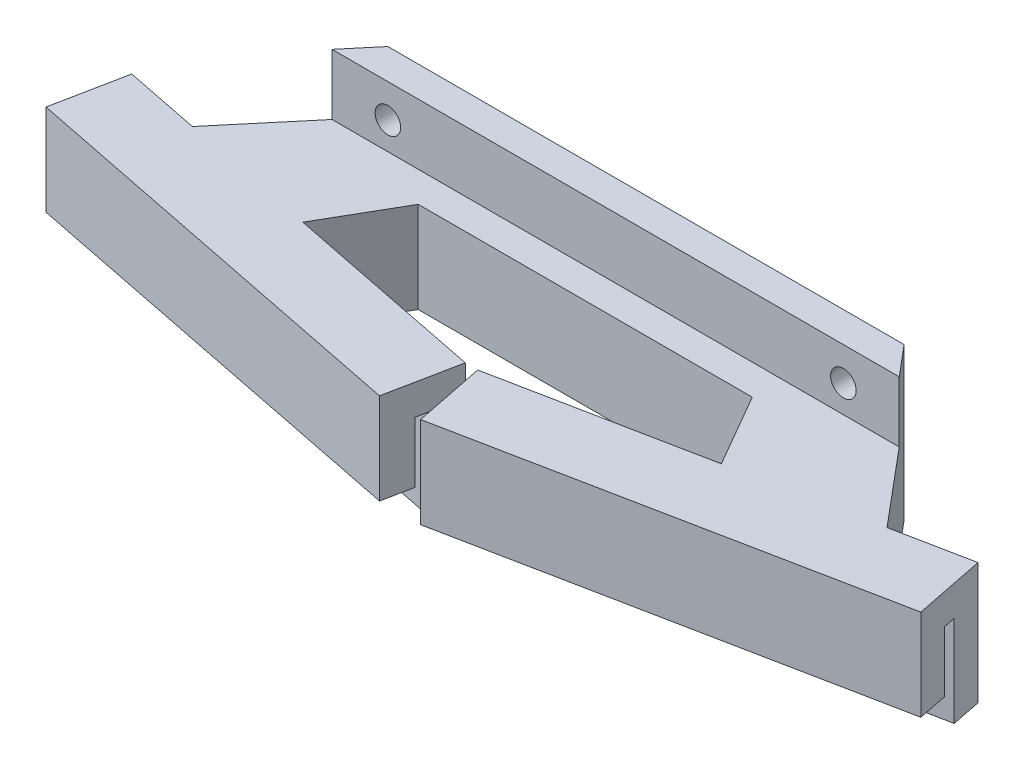
SolidWorks part; units mm, degrees
material "ABS"
ref_plane "Front Plane" through (0, 0, 0) normal (0, 0, 1) x (1, 0, 0)
ref_plane "Top Plane" through (0, 0, 0) normal (0, 1, 0) x (1, 0, 0)
ref_plane "Right Plane" through (0, 0, 0) normal (1, 0, 0) x (0, 0, -1)
ref_axis "X" through (-88.99, 0, 0) along (1, 0, 0)
ref_axis "Y" through (0, 55, 0) along (0, -1, 0)
ref_axis "Z" through (0, 0, -88.99) along (0, 0, 1)
sketch "Sketch1" plane through (0, 0, 0) normal (0, 1, 0) x (1, 0, 0)
  line L0 (27.1702, -94.8196) -> (27.5625, -96.7807) construction
  line L1 (27.1702, -94.8196) -> (27.5625, -96.7807)
  line L2 (22.7661, -96.7807) -> (23.1583, -94.8196) construction
  line L3 (-45.8746, -83.0526) -> (22.7661, -96.7807) construction
  line L4 (22.7661, -96.7807) -> (23.1583, -94.8196)
  line L5 (27.5625, -96.7807) -> (96.2031, -83.0526) construction
  line L6 (23.1583, -94.8196) -> (-45.4823, -81.0914)
  line L7 (-45.4823, -81.0914) -> (-45.8746, -83.0526)
  line L8 (-45.8746, -83.0526) -> (22.7661, -96.7807)
  line L9 (27.1702, -94.8196) -> (95.8109, -81.0914)
  line L10 (95.8109, -81.0914) -> (96.2031, -83.0526)
  line L11 (96.2031, -83.0526) -> (27.5625, -96.7807)
  dimension "D3" = 2
  dimension "D4" = 2
  dimension "D7" = 70
  dimension "D8" = 70
extrude "Boss-Extrude1" add sketch "Sketch1" along normal blind 5
sketch "Sketch2" plane through (0, 5, 0) normal (0, 1, 0) x (1, 0, 0)
  line L0 (0, 0) -> (0, 33.2136) construction
  line L1 (22.9622, -95.8001) -> (-45.6785, -82.072) construction
  line L2 (22.7661, -96.7807) -> (23.1583, -94.8196) construction
  line L3 (-45.4823, -81.0914) -> (-45.8746, -83.0526) construction
  line L4 (-45.4823, -81.0914) -> (-44.5018, -76.1885)
  line L5 (-44.5018, -76.1885) -> (24.1389, -89.9167)
  line L6 (24.1389, -89.9167) -> (23.1583, -94.8196)
  line L7 (23.1583, -94.8196) -> (-45.4823, -81.0914) construction
  line L8 (23.1583, -94.8196) -> (-45.4823, -81.0914)
  line L9 (21.7855, -101.6836) -> (22.7661, -96.7807)
  line L10 (-46.8552, -87.9555) -> (21.7855, -101.6836)
  line L11 (-45.8746, -83.0526) -> (-46.8552, -87.9555)
  line L12 (22.7661, -96.7807) -> (-45.8746, -83.0526)
  line L21 (27.1702, -94.8196) -> (26.1896, -89.9167)
  line L22 (26.1896, -89.9167) -> (94.8303, -76.1885)
  line L23 (94.8303, -76.1885) -> (95.8109, -81.0914)
  line L24 (96.2031, -83.0526) -> (95.8109, -81.0914) construction
  line L25 (95.8109, -81.0914) -> (27.1702, -94.8196) construction
  line L26 (95.8109, -81.0914) -> (27.1702, -94.8196)
  line L27 (27.3663, -95.8001) -> (96.007, -82.072) construction
  line L28 (27.1702, -94.8196) -> (27.5625, -96.7807) construction
  line L29 (97.1837, -87.9555) -> (96.2031, -83.0526)
  line L30 (28.543, -101.6836) -> (97.1837, -87.9555)
  line L31 (27.5625, -96.7807) -> (28.543, -101.6836)
  line L32 (96.2031, -83.0526) -> (27.5625, -96.7807)
  dimension "D1" = 5
  dimension "D2" = 5
extrude "Boss-Extrude2" add sketch "Sketch2" against normal blind 20
ref_plane "Plane1" through (0, -10, 0) normal (0, 1, 0) x (1, 0, 0)
sketch "Sketch3" plane through (0, -10, 0) normal (0, 1, 0) x (1, 0, 0)
  line L0 (25.1643, -107.258) -> (25.1643, -89.9167) construction
  line L1 (-17.3357, -61.1885) -> (67.6643, -61.1885)
  line L3 (-2.3357, -71.1885) -> (52.6643, -71.1885)
  line L5 (24.1389, -89.9167) -> (26.1896, -89.9167) construction
  line L6 (-17.3357, -61.1885) -> (-32.0174, -78.6854)
  line L7 (24.1389, -89.9167) -> (-44.5018, -76.1885) construction
  line L8 (-2.3357, -71.1885) -> (-9.2886, -83.2312)
  line L9 (67.6643, -61.1885) -> (82.3459, -78.6854)
  line L10 (94.8303, -76.1885) -> (26.1896, -89.9167) construction
  line L11 (52.6643, -71.1885) -> (59.6171, -83.2312)
  line L12 (-32.0174, -78.6854) -> (-9.2886, -83.2312)
  line L13 (59.6171, -83.2312) -> (82.3459, -78.6854)
  point P5 (25.1643, -71.1885)
  point P10 (25.1643, -89.9167)
  dimension "D1" = 10
  dimension "D2" = 15
  dimension "D3" = 15
  dimension "D4" = 85
  dimension "D5" = 120
  dimension "D6" = 120
  dimension "D7" = 130
  dimension "D8" = 130
  dimension "D9" = 15
extrude "Boss-Extrude3" add sketch "Sketch3" along normal blind 5
sketch "Sketch4" plane through (0, -5, 0) normal (0, 1, 0) x (1, 0, 0)
  line L0 (-17.3357, -61.1885) -> (-17.3357, -56.1885)
  line L1 (-17.3357, -56.1885) -> (67.6643, -56.1885)
  line L2 (67.6643, -56.1885) -> (67.6643, -61.1885)
  line L3 (67.6643, -61.1885) -> (-17.3357, -61.1885)
  dimension "D1" = 5
extrude "Boss-Extrude4" add sketch "Sketch4" against normal up to surface (5 mm away) up to face at (25.1643, -10, 73.5734)
sketch "Sketch5" plane through (0, -5, 0) normal (0, 1, 0) x (1, 0, 0)
  line L0 (25.1643, -71.1885) -> (25.1643, -56.1885) construction
  line L7 (-21.5312, -66.1885) -> (71.8598, -66.1885)
  line L9 (-2.3357, -71.1885) -> (52.6643, -71.1885) construction
  line L10 (67.6643, -56.1885) -> (-17.3357, -56.1885) construction
  line L13 (82.3459, -78.6854) -> (67.6643, -61.1885) construction
  line L14 (-17.3357, -61.1885) -> (67.6643, -61.1885)
  line L16 (-17.3357, -56.1885) -> (-17.3357, -61.1885) construction
  line L17 (67.6643, -61.1885) -> (67.6643, -56.1885) construction
  line L18 (67.6643, -61.1885) -> (71.8598, -66.1885)
  line L19 (-21.5312, -66.1885) -> (-17.3357, -61.1885)
  point P10 (25.1643, -66.1885)
  dimension "D1" = 5
  dimension "D3" = 5
extrude "Boss-Extrude5" add sketch "Sketch5" along normal blind 20
sketch "Sketch7" plane through (0, 0, 66.1885) normal (0, 0, 1) x (1, 0, 0)
  line L0 (-12.3357, 9.5) -> (62.6643, 9.5) construction
  line L1 (25.1643, 15) -> (25.1643, -5) construction
  line L2 (-21.5312, 15) -> (71.8598, 15) construction
  line L3 (-2.3357, -5) -> (52.6643, -5) construction
  line L4 (-21.5312, -5) -> (71.8598, -5) construction
  circle A0 centre (-12.3357, 9.5) radius 2.1
  circle A1 centre (62.6643, 9.5) radius 2.1
  point P10 (25.1643, 9.5)
  dimension "D1" = 4.2
  dimension "D2" = 75
  dimension "D3" = 14.5
extrude "Cut-Extrude1" cut sketch "Sketch7" against normal up to surface (5 mm away) up to face at (25.1643, 5, 61.1885)
sketch "Sketch8" plane through (0, -5, 0) normal (0, 1, 0) x (1, 0, 0)
  line L0 (59.6171, -83.2312) -> (82.3459, -78.6854) construction
  line L1 (52.6643, -71.1885) -> (59.6171, -83.2312) construction
  line L2 (82.3459, -78.6854) -> (71.8598, -66.1885) construction
  line L3 (-2.3357, -71.1885) -> (52.6643, -71.1885) construction
  line L4 (-9.2886, -83.2312) -> (-2.3357, -71.1885) construction
  line L5 (-21.5312, -66.1885) -> (71.8598, -66.1885) construction
  line L6 (-32.0174, -78.6854) -> (-9.2886, -83.2312) construction
  line L7 (-21.5312, -66.1885) -> (-32.0174, -78.6854) construction
  line L8 (59.6171, -83.2312) -> (82.3459, -78.6854)
  line L9 (52.6643, -71.1885) -> (59.6171, -83.2312)
  line L10 (82.3459, -78.6854) -> (71.8598, -66.1885)
  line L11 (-2.3357, -71.1885) -> (52.6643, -71.1885)
  line L12 (-9.2886, -83.2312) -> (-2.3357, -71.1885)
  line L13 (-21.5312, -66.1885) -> (71.8598, -66.1885)
  line L14 (-32.0174, -78.6854) -> (-9.2886, -83.2312)
  line L15 (-21.5312, -66.1885) -> (-32.0174, -78.6854)
extrude "Boss-Extrude6" add sketch "Sketch8" along normal up to surface (10 mm away) up to face at (-11.3581, 5, 88.9361)
sketch "Sketch11" plane through (0, -5, 0) normal (0, 1, 0) x (1, 0, 0)
  line L1 (-17.3357, -56.1885) -> (67.6643, -56.1885)
  line L2 (-17.3357, -56.1885) -> (-17.3357, -61.1885)
  line L3 (-17.3357, -61.1885) -> (67.6643, -61.1885)
  line L4 (67.6643, -56.1885) -> (67.6643, -61.1885)
extrude "Cut-Extrude2" cut sketch "Sketch11" against normal up to surface (5 mm away) up to face at (25.1643, -10, 70.0964)
sketch "Sketch12" plane through (0, -15, 0) normal (0, -1, 0) x (1, 0, 0)
  line L0 (97.1837, 87.9555) -> (28.543, 101.6836) construction
  line L1 (28.543, 101.6836) -> (27.5625, 96.7807) construction
  line L2 (27.5625, 96.7807) -> (96.2031, 83.0526) construction
  line L3 (96.2031, 83.0526) -> (97.1837, 87.9555) construction
  line L4 (21.7855, 101.6836) -> (-46.8552, 87.9555) construction
  line L5 (-46.8552, 87.9555) -> (-45.8746, 83.0526) construction
  line L6 (-45.8746, 83.0526) -> (22.7661, 96.7807) construction
  line L7 (22.7661, 96.7807) -> (21.7855, 101.6836) construction
  line L8 (97.1837, 87.9555) -> (28.543, 101.6836)
  line L9 (28.543, 101.6836) -> (27.5625, 96.7807)
  line L10 (27.5625, 96.7807) -> (96.2031, 83.0526)
  line L11 (96.2031, 83.0526) -> (97.1837, 87.9555)
  line L12 (21.7855, 101.6836) -> (-46.8552, 87.9555)
  line L13 (-46.8552, 87.9555) -> (-45.8746, 83.0526)
  line L14 (-45.8746, 83.0526) -> (22.7661, 96.7807)
  line L15 (22.7661, 96.7807) -> (21.7855, 101.6836)
extrude "Cut-Extrude3" cut sketch "Sketch12" against normal blind 5
